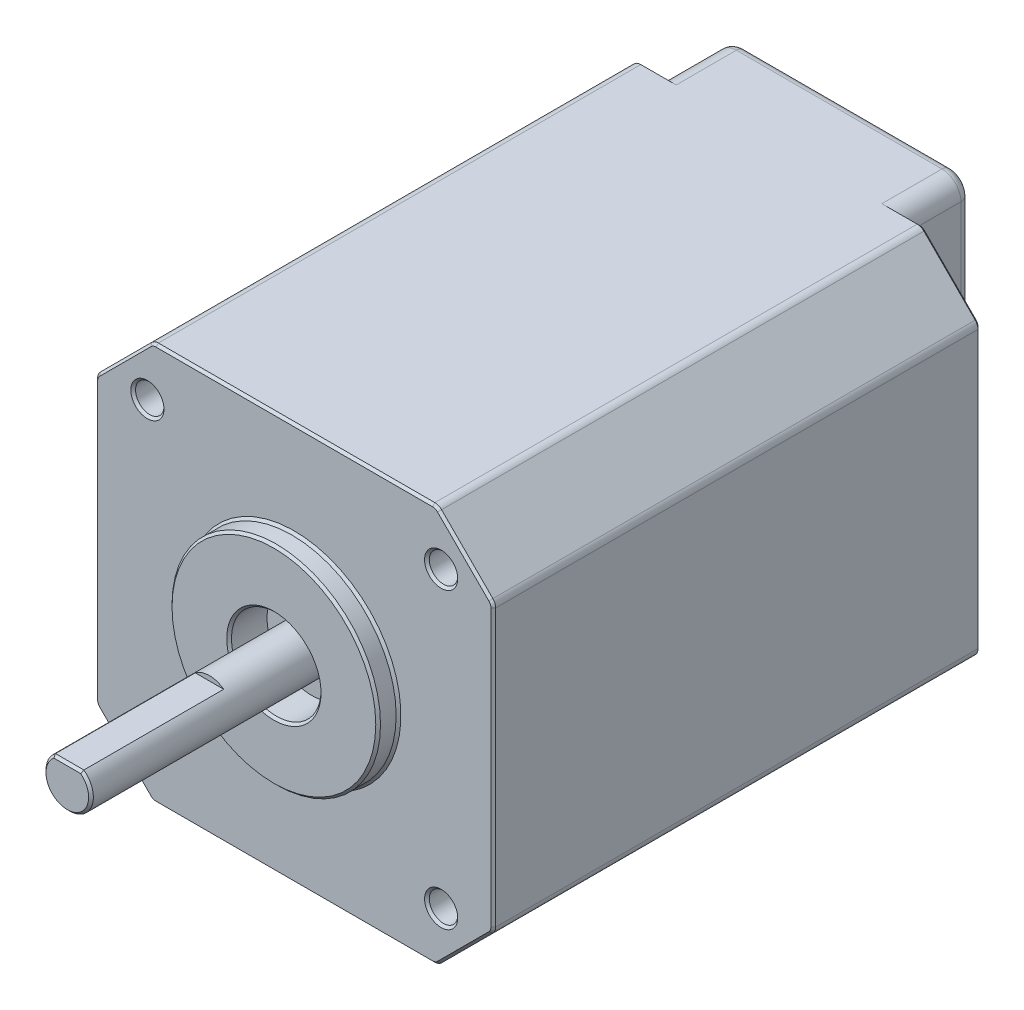
SolidWorks part; units mm, degrees
ref_plane "Front Plane" through (0, 0, 0) normal (0, 0, 1) x (1, 0, 0)
ref_plane "Top Plane" through (0, 0, 0) normal (0, 1, 0) x (1, 0, 0)
ref_plane "Right Plane" through (0, 0, 0) normal (1, 0, 0) x (0, 0, -1)
sketch "Sketch1" plane through (0, 0, 0) normal (0, 0, 1) x (1, 0, 0)
  line L0 (-21, 15) -> (-15, 21)
  line L1 (-15, 21) -> (15, 21)
  line L2 (-21, 15) -> (-21, -15)
  line L3 (-15, -21) -> (15, -21)
  line L4 (21, 15) -> (21, -15)
  line L5 (-21, 21) -> (21, -21) construction
  line L6 (-21, -21) -> (21, 21) construction
  line L7 (15, 21) -> (21, 15)
  line L8 (15, -21) -> (21, -15)
  line L9 (-21, -15) -> (-15, -21)
  point P0 (0, 0)
  dimension "D1" = 42
extrude "Boss-Extrude1" add sketch "Sketch1" against normal blind 51.4
sketch "Sketch2" plane through (0, 0, 0) normal (0, 0, 1) x (1, 0, 0)
  line L0 (-4.338, 0) -> (4.614, 0) construction
  line L1 (0, 6.6252) -> (0, -4.0225) construction
  line L2 (-15.5, 15.5) -> (15.5, 15.5) construction
  line L3 (-15.5, 15.5) -> (-15.5, -15.5) construction
  circle A0 centre (-15.5, 15.5) radius 1.5
  circle A1 centre (15.5, 15.5) radius 1.5
  circle A2 centre (15.5, -15.5) radius 1.5
  circle A3 centre (-15.5, -15.5) radius 1.5
  dimension "D1" = 3
  dimension "D2" = 31
extrude "Cut-Extrude1" cut sketch "Sketch2" against normal blind 4.5
sketch "Sketch3" plane through (0, 0, 0) normal (0, 0, 1) x (1, 0, 0)
  circle A0 centre (0, 0) radius 11
  dimension "D1" = 22
extrude "Boss-Extrude2" add sketch "Sketch3" along normal blind 2.15
sketch "Sketch5" plane through (0, 0, 2.15) normal (0, 0, 1) x (1, 0, 0)
  circle A0 centre (0, 0) radius 4.725
  dimension "D1" = 9.45
extrude "Cut-Extrude2" cut sketch "Sketch5" against normal blind 4
sketch "Sketch4" plane through (0, 0, -1.85) normal (0, 0, 1) x (1, 0, 0)
  circle A0 centre (0, 0) radius 2.5
  dimension "D1" = 5
extrude "Boss-Extrude3" add sketch "Sketch4" along normal offset from surface (25.8 mm away) 21.8 up to face at (4.725, 0, 2.15) offset beyond the face yes
sketch "Sketch6" plane through (0, 0, 23.95) normal (0, 0, 1) x (1, 0, 0)
  line L0 (-1.5, 2) -> (1.5, 2)
  circle A1 centre (0, 0) radius 2.5
  arc A2 (1.5, 2) -> (-1.5, 2) centre (0, 0) ccw
  point P5 (0, -2.5)
  dimension "D2" = 4.5
  dimension "D1" = 0
extrude "Cut-Extrude3" cut sketch "Sketch6" against normal blind 15
sketch "Sketch7" plane through (0, 0, -51.4) normal (0, 0, -1) x (-1, 0, 0)
  line L0 (0, 11.9885) -> (0, -5.521) construction
  line L1 (-15, 21) -> (15, 21) construction
  line L2 (-12.85, 7.1) -> (12.85, 7.1)
  line L3 (-12.85, 7.1) -> (-12.85, 21)
  line L4 (-12.85, 21) -> (12.85, 21)
  line L5 (12.85, 7.1) -> (12.85, 21)
  line L6 (-12.85, 7.1) -> (12.85, 21) construction
  line L7 (-12.85, 21) -> (12.85, 7.1) construction
  point P1 (0, 14.05)
  dimension "D1" = 25.7
  dimension "D2" = 13.9
extrude "Boss-Extrude4" add sketch "Sketch7" along normal offset from surface (7.1 mm away) 58.5 up to face at (11, 0, 0)
fillet "Fillet1" radius 1 12 edges at (15, 21, -25.7) (21, 15, -25.7) (21, -15, -25.7) (15, -21, -25.7) (-15, -21, -25.7) (-21, -15, -25.7) (-15, 21, -25.7) (-21, 15, -25.7) (12.85, 14.05, -58.5) (0, 21, -58.5) (-12.85, 14.05, -58.5) (0, 7.1, -58.5)
fillet "Fillet2" radius 2 8 edges at (12.85, 7.1, -54.45) (12.85, 21, -54.45) (-12.85, 7.1, -54.45) (-12.85, 21, -54.45) (-12.5571, 20.7071, -58.2071) (-12.5571, 7.3929, -58.2071) (12.5571, 20.7071, -58.2071) (12.5571, 7.3929, -58.2071)
chamfer "Chamfer1" distance 0.25 angle 45 42 edges at (0, -2.5, 23.95) (0, 2, 23.95) (11, 0, 2.15) (4.725, 0, 2.15) (20.9239, 14.9685, 0) (21, 0, 0) (20.9239, -14.9685, 0) (18, -18, 0) (14.9685, -20.9239, 0) (0, -21, 0) (-14.9685, -20.9239, 0) (-18, -18, 0) (-20.9239, -14.9685, 0) (-21, 0, 0) (-20.9239, 14.9685, 0) (-18, 18, 0) (-14.9685, 20.9239, 0) (0, 21, 0) (14.9685, 20.9239, 0) (18, 18, 0) (-14, 15.5, 0) (14, 15.5, 0) (17, -15.5, 0) (-17, -15.5, 0) (11, 0, 0) (12.7179, 21, -51.4) (14.9685, 20.9239, -51.4) (18, 18, -51.4) (20.9239, 14.9685, -51.4) (21, 0, -51.4) (20.9239, -14.9685, -51.4) (18, -18, -51.4) (14.9685, -20.9239, -51.4) (-12.7179, 21, -51.4) (0, -21, -51.4) (-14.9685, 20.9239, -51.4) (-14.9685, -20.9239, -51.4) (-18, 18, -51.4) (-18, -18, -51.4) (-20.9239, 14.9685, -51.4) (-20.9239, -14.9685, -51.4) (-21, 0, -51.4)
